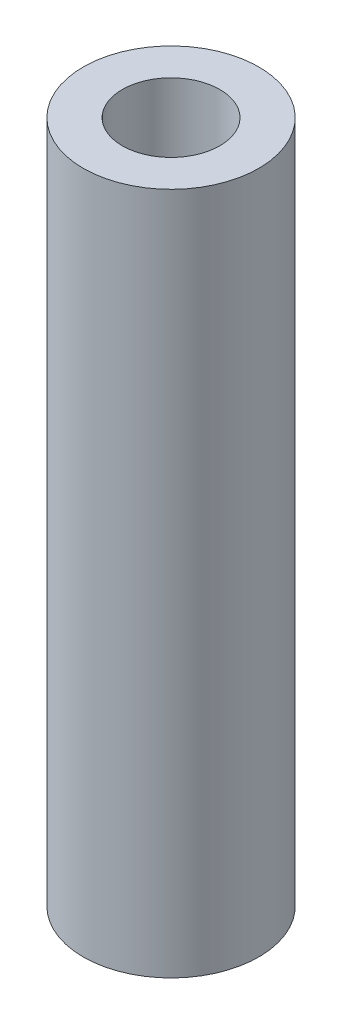
SolidWorks part; units mm, degrees
material "EPDM"
ref_plane "Płaszczyzna przednia" through (0, 0, 0) normal (0, 0, 1) x (1, 0, 0)
ref_plane "Płaszczyzna górna" through (0, 0, 0) normal (0, 1, 0) x (1, 0, 0)
ref_plane "Płaszczyzna prawa" through (0, 0, 0) normal (1, 0, 0) x (0, 0, -1)
sketch "Szkic1" plane through (0, 0, 0) normal (0, 0, 1) x (1, 0, 0)
  line L0 (0, 344.7443) -> (0, -336.9732) construction
  line L1 (35, 245) -> (63, 245)
  line L2 (35, 245) -> (35, -245)
  line L3 (35, -245) -> (63, -245)
  line L4 (63, 245) -> (63, -245)
  point P4 (35, 0)
  dimension "D1" = 63
  dimension "D2" = 35
  dimension "D3" = 490
revolve "Obrót1" add sketch "Szkic1" angle 360 about L0
